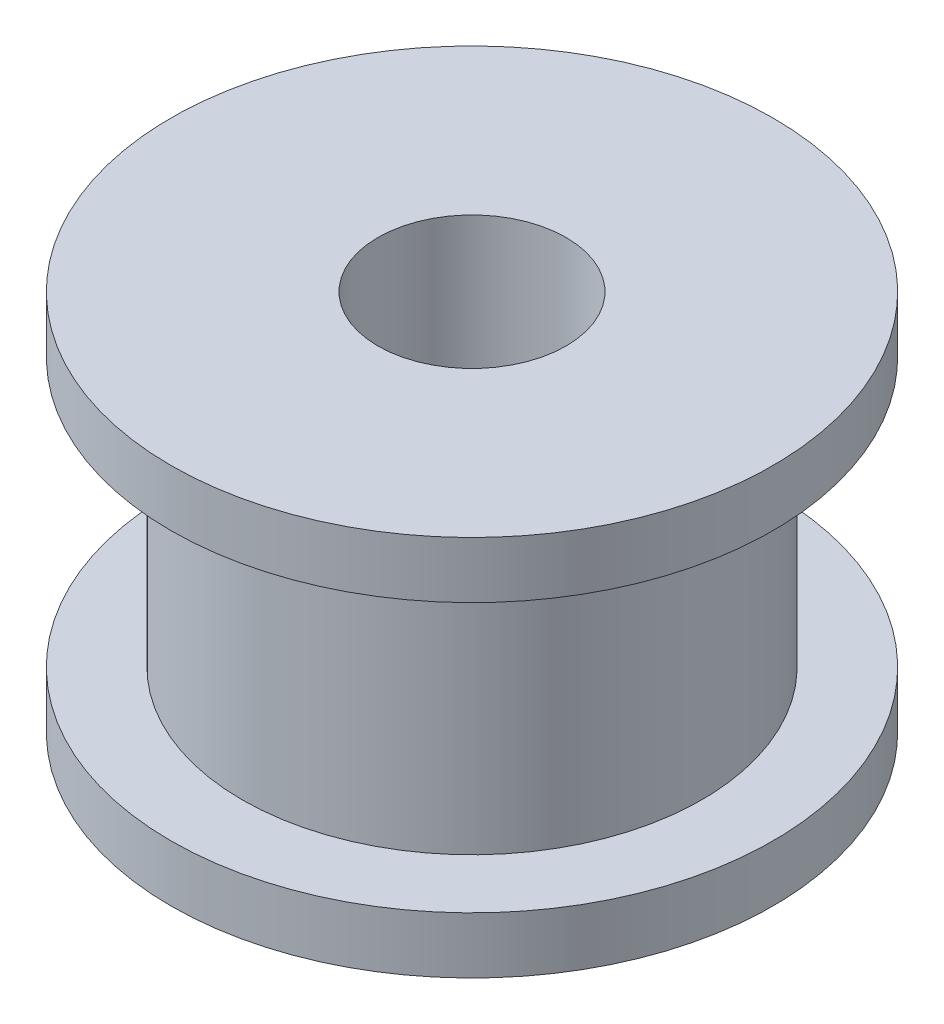
SolidWorks part; units mm, degrees
ref_plane "Front Plane" through (0, 0, 0) normal (0, 0, 1) x (1, 0, 0)
ref_plane "Top Plane" through (0, 0, 0) normal (0, 1, 0) x (1, 0, 0)
ref_plane "Right Plane" through (0, 0, 0) normal (1, 0, 0) x (0, 0, -1)
sketch "Sketch1" plane through (0, 0, 0) normal (0, 1, 0) x (1, 0, 0)
  circle A0 centre (0, 0) radius 8
extrude "Boss-Extrude1" add sketch "Sketch1" along normal blind 7.1
sketch "Sketch2" plane through (0, 7.1, 0) normal (0, 1, 0) x (1, 0, 0)
  circle A0 centre (0, 0) radius 6.11
extrude "Boss-Extrude2" add sketch "Sketch2" along normal blind 7.14
sketch "Sketch5" plane through (0, 0, 0) normal (0, -1, 0) x (1, 0, 0)
  circle A0 centre (0, 0) radius 2.5
extrude "Cut-Extrude2" cut sketch "Sketch5" against normal blind 16
sketch "Sketch8" plane through (0, 14.24, 0) normal (0, 1, 0) x (1, 0, 0)
  circle A0 centre (0, 0) radius 8
extrude "Boss-Extrude4" add sketch "Sketch8" along normal blind 1.5
sketch "Sketch9" plane through (0, 15.74, 0) normal (0, 1, 0) x (1, 0, 0)
  circle A0 centre (0, 0) radius 2.5
extrude "Cut-Extrude4" cut sketch "Sketch9" against normal up to surface (15.74 mm away) up to face at (0, 0, -2.5)
sketch "Sketch10" plane through (0, 0, 0) normal (1, 0, 0) x (0, 0, -1)
  line L0 (8, 7.1) -> (-8, 7.1) construction
  line L1 (-8, 5.6) -> (8, 5.6)
  line L2 (-8, 5.6) -> (-8, -0.4)
  line L3 (-8, -0.4) -> (8, -0.4)
  line L4 (8, 5.6) -> (8, -0.4)
  line L5 (-8, 7.1) -> (-8, 0) construction
  dimension "D1" = 1.5
  dimension "D2" = 16
  dimension "D3" = 0
  dimension "D4" = 6
extrude "Cut-Extrude5" cut sketch "Sketch10" against normal blind 10 and the other way blind 10
